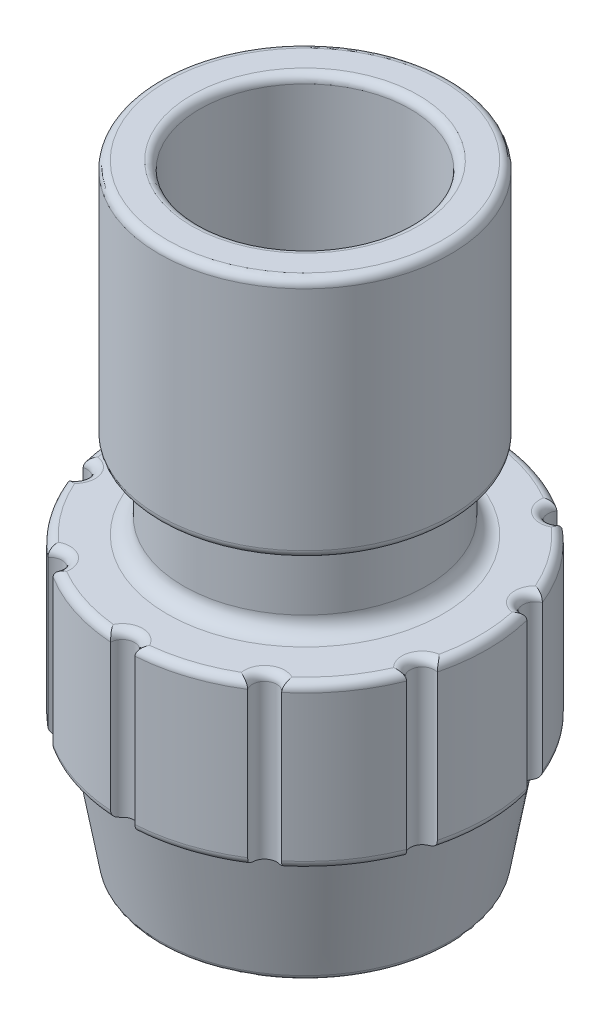
SolidWorks part; units mm, degrees
material "PE Высокой плотности"
ref_plane "Front" through (0, 0, 0) normal (0, 0, 1) x (1, 0, 0)
ref_plane "Top" through (0, 0, 0) normal (0, 1, 0) x (1, 0, 0)
ref_plane "Right" through (0, 0, 0) normal (1, 0, 0) x (0, 0, -1)
sketch "Эскиз1" plane through (0, 0, 0) normal (0, 1, 0) x (1, 0, 0)
  circle A0 centre (0, 0) radius 16
  dimension "D1" = 32
extrude "Вытянуть-Тонкостенный1" add sketch "Эскиз1" along normal blind 15 draft 10 thin draft outward yes thin type one direction wall 1.9
sketch "Эскиз2" plane through (0, 15, 0) normal (0, 1, 0) x (1, 0, 0)
  circle A2 centre (0, 0) radius 22.5449
  circle A3 centre (0, 0) radius 22.5449
  dimension "D1" = 2
extrude "Бобышка-Вытянуть1" add sketch "Эскиз2" along normal blind 20
fillet "Скругление1" radius 0.7 2 edges at (0, 0, 16) (17.9, 0, 0)
fillet "Скругление2" radius 1 1 edges at (0, 15, 22.5449)
sketch "Эскиз3" plane through (0, 35, 0) normal (0, 1, 0) x (1, 0, 0)
  line L0 (0, 0) -> (0, 22.5449) construction
  circle A0 centre (0, 22.5449) radius 1.5
  dimension "D1" = 3
extrude "Вырез-Вытянуть1" cut sketch "Эскиз3" against normal through all
sketch3d "Трехмерный эскиз1"
  line L0 (0, 35, 0) -> (0, 0, 0) construction
ref_axis "Ось1" through (0, 35, 0) along (0, -1, 0)
pattern_circular "Круговой массив1" count 10 over 360 about axis through (0, 35, 0) along (0, -1, 0) of "Вырез-Вытянуть1"
sketch "Эскиз4" plane through (0, 35, 0) normal (0, 1, 0) x (1, 0, 0)
  circle A0 centre (0, 0) radius 15
  dimension "D1" = 30
extrude "Бобышка-Вытянуть2" add sketch "Эскиз4" along normal blind 10
fillet "Скругление3" radius 2 1 edges at (0, 35, 15)
sketch "Эскиз5" plane through (0, 45, 0) normal (0, 1, 0) x (1, 0, 0)
  circle A1 centre (0, 0) radius 18
  dimension "D1" = 36
extrude "Бобышка-Вытянуть3" add sketch "Эскиз5" along normal blind 30
sketch "Эскиз6" plane through (0, 75, 0) normal (0, 1, 0) x (1, 0, 0)
  circle A0 centre (0, 0) radius 13
  dimension "D1" = 26
extrude "Вырез-Вытянуть2" cut sketch "Эскиз6" against normal through all
fillet "Скругление4" radius 1 1 edges at (0, 45, 18)
fillet "Скругление5" radius 1 2 edges at (0, 75, 18) (0, 75, 13)
fillet "Скругление6" radius 1 20 edges at (-6.9668, 35, -21.4415) (0, 35, -21.0449) (6.9668, 35, -21.4415) (12.3699, 35, -17.0257) (18.2392, 35, -13.2516) (20.0149, 35, -6.5032) (22.5449, 35, 0) (20.0149, 35, 6.5032) (18.2392, 35, 13.2516) (12.3699, 35, 17.0257) (6.9668, 35, 21.4415) (0, 35, 21.0449) (-6.9668, 35, 21.4415) (-12.3699, 35, 17.0257) (-18.2392, 35, 13.2516) (-20.0149, 35, 6.5032) (-22.5449, 35, 0) (-20.0149, 35, -6.5032) (-18.2392, 35, -13.2516) (-12.3699, 35, -17.0257)
